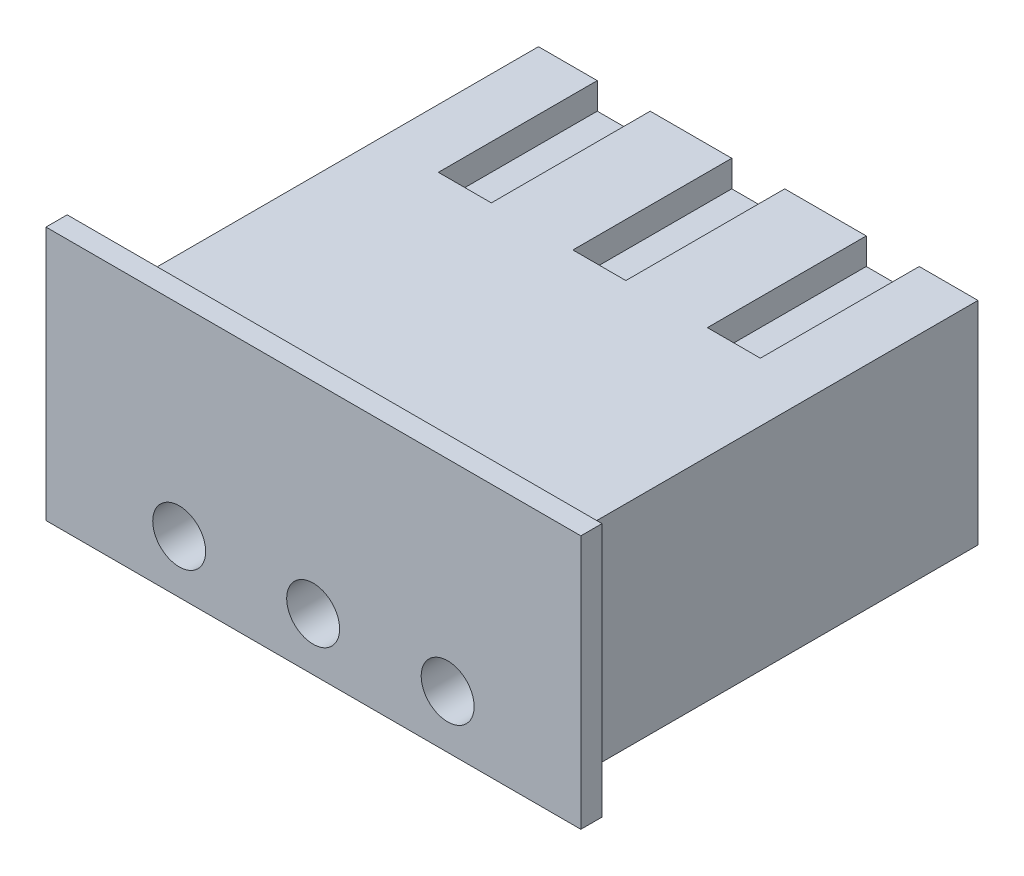
SolidWorks part; units mm, degrees
material "PEI"
ref_plane "前视基准面" through (0, 0, 0) normal (0, 0, 1) x (1, 0, 0)
ref_plane "上视基准面" through (0, 0, 0) normal (0, 1, 0) x (1, 0, 0)
ref_plane "右视基准面" through (0, 0, 0) normal (1, 0, 0) x (0, 0, -1)
other "Configuration Table"
sketch "草图2" plane through (0, 0, 0) normal (0, 0, 1) x (1, 0, 0)
  line L1 (0, 0) -> (8.3, 0)
  line L2 (0, 0) -> (0, 4)
  line L3 (0, 4) -> (8.3, 4)
  line L4 (8.3, 0) -> (8.3, 4)
  dimension "D1" = 8.3
  dimension "D2" = 4
extrude "凸台-拉伸1" add sketch "草图2" along normal blind 8
sketch "草图3" plane through (0, 0, 8) normal (0, 0, 1) x (1, 0, 0)
  line L0 (0, 4) -> (0, 0) construction
  line L1 (-0.9, 0) -> (9.2, 0)
  line L2 (-0.9, 0) -> (-0.9, 4.8)
  line L3 (-0.9, 4.8) -> (9.2, 4.8)
  line L4 (9.2, 0) -> (9.2, 4.8)
  line L5 (8.3, 0) -> (8.3, 4) construction
  line L6 (8.3, 4) -> (0, 4) construction
  dimension "D1" = 0.9
  dimension "D2" = 0.9
  dimension "D3" = 0.8
extrude "凸台-拉伸2" add sketch "草图3" along normal blind 0.4
sketch "草图4" plane through (0, 0, 0) normal (0, 0, -1) x (-1, 0, 0)
  line L0 (-4.15, 4) -> (-4.15, 0) construction
  line L1 (-8.3, 4) -> (0, 4) construction
  line L2 (0, 0) -> (-8.3, 0) construction
  line L3 (-8.3, 4) -> (0, 4) construction
  line L4 (-4.65, 4) -> (-3.65, 4)
  line L5 (-4.65, 4) -> (-4.65, 3.5)
  line L6 (-4.65, 3.5) -> (-3.65, 3.5)
  line L7 (-3.65, 4) -> (-3.65, 3.5)
  line L9 (-7.19, 4) -> (-6.19, 4)
  line L10 (-7.19, 4) -> (-7.19, 3.5)
  line L11 (-7.19, 3.5) -> (-6.19, 3.5)
  line L12 (-6.19, 4) -> (-6.19, 3.5)
  line L13 (-2.11, 4) -> (-1.11, 4)
  line L14 (-2.11, 4) -> (-2.11, 3.5)
  line L15 (-2.11, 3.5) -> (-1.11, 3.5)
  line L16 (-1.11, 4) -> (-1.11, 3.5)
  dimension "D1" = 1
  dimension "D2" = 2.54
  dimension "D3" = 0.5
extrude "切除-拉伸1" cut sketch "草图4" against normal blind 3 and the other way through all
sketch "草图5" plane through (0, 0, 0) normal (0, 0, -1) x (-1, 0, 0)
  line L0 (-4.15, 4) -> (-4.15, 0) construction
  line L1 (-8.3, 4) -> (0, 4) construction
  line L2 (0, 0) -> (-8.3, 0) construction
  circle A0 centre (-6.6848, 1) radius 0.5
  circle A1 centre (-4.1448, 1) radius 0.5
  circle A2 centre (-1.6152, 1) radius 0.5
  point P6 (0, 0)
  point P13 (0, 0)
  point P14 (0, 0)
  point P15 (0, 0)
  dimension "D3" = 1
  dimension "D1" = 2.54
  dimension "D2" = 1
extrude "切除-拉伸2" cut sketch "草图5" against normal blind 10
other "连接点1" parameters "直径"=4, "端头长度"=6
ref_axis "基准轴1" through (6.6848, 1, 8.4) along (0, 0, -1)
other "连接点2" parameters "直径"=4, "端头长度"=6
ref_axis "基准轴2" through (4.1448, 1, 8.4) along (0, 0, -1)
other "连接点3" parameters "直径"=4, "端头长度"=6
ref_axis "基准轴3" through (1.6152, 1, 8.4) along (0, 0, -1)
